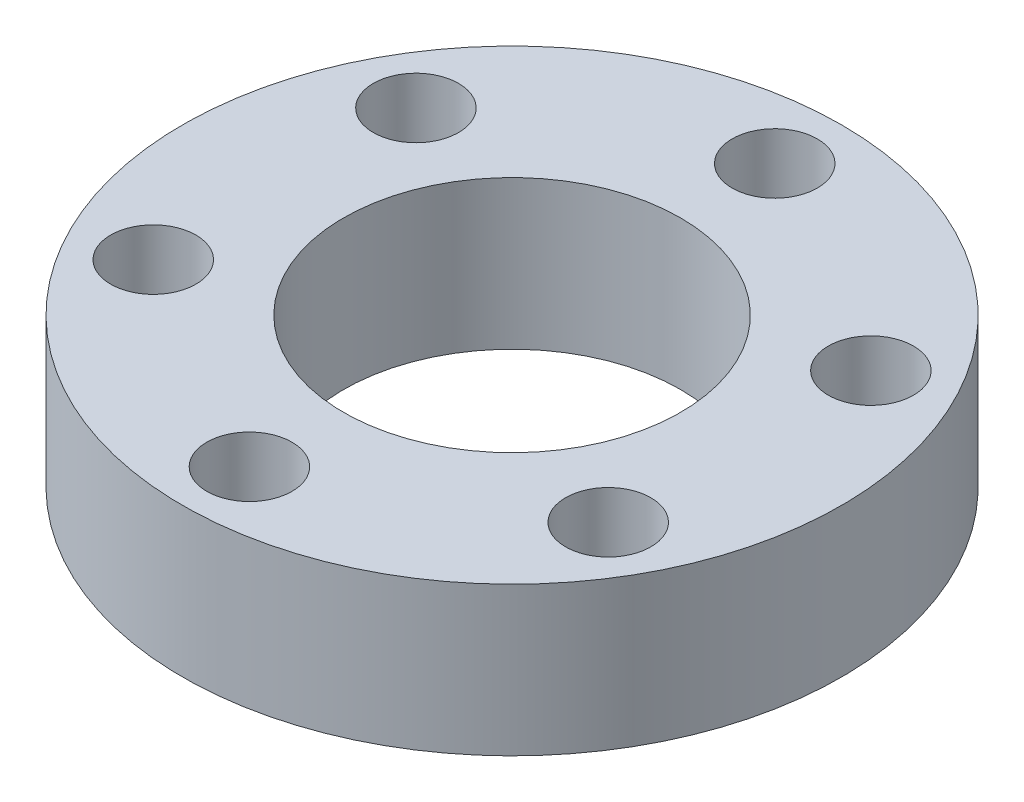
SolidWorks part; units mm, degrees
ref_plane "Front Plane" through (0, 0, 0) normal (0, 0, 1) x (1, 0, 0)
ref_plane "Top Plane" through (0, 0, 0) normal (0, 1, 0) x (1, 0, 0)
ref_plane "Right Plane" through (0, 0, 0) normal (1, 0, 0) x (0, 0, -1)
sketch "Sketch1" plane through (0, 0, 0) normal (0, 1, 0) x (1, 0, 0)
  circle A0 centre (0, 0) radius 16.891
  dimension "D1" = 33.782
extrude "Extrude1" add sketch "Sketch1" along normal blind 7.62
sketch "Sketch2" plane through (0, 0, 0) normal (0, 1, 0) x (1, 0, 0)
  circle A0 centre (0, 0) radius 8.636
  dimension "D1" = 17.272
extrude "Cut-Extrude4" cut sketch "Sketch2" along normal through all
sketch "Sketch3" plane through (0, 0, 0) normal (0, 1, 0) x (1, 0, 0)
  circle A0 centre (0, 13.462) radius 2.1844
  dimension "D2" = 4.3688
  dimension "D1" = 13.462
extrude "Cut-Extrude6" cut sketch "Sketch3" along normal blind 7.62
ref_axis "Axis1" through (0, 17.3423, 0) along (0, -1, 0)
pattern_circular "CirPattern1" count 6 over 360 about axis through (0, 17.3423, 0) along (0, -1, 0) of "Cut-Extrude6"
sketch "Sketch4" plane through (0, 0, 0) normal (0, 1, 0) x (1, 0, 0)
  line L0 (0, 0) -> (0, 5.3021)
sketch "Sketch5" plane through (0, 0, 0) normal (0, 1, 0) x (1, 0, 0)
  line L0 (0, 0) -> (0, 7.0663)
